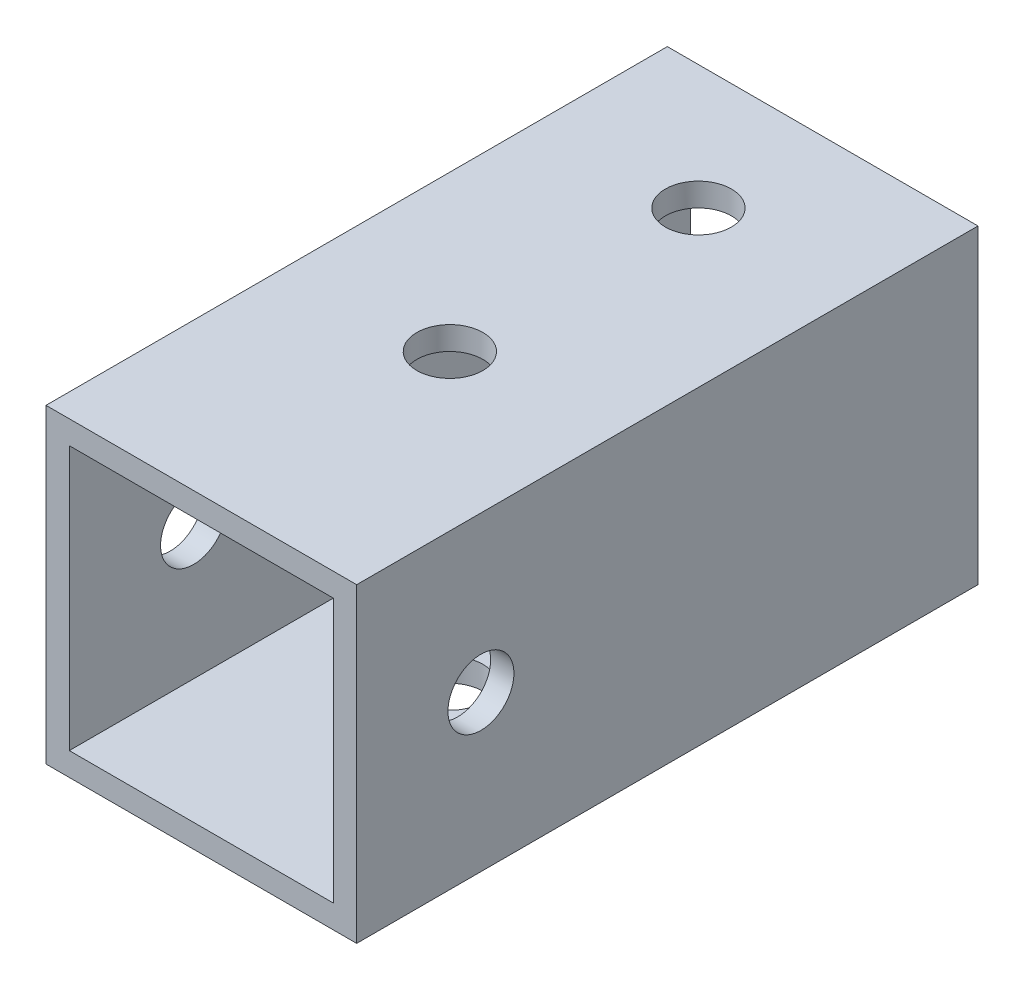
SolidWorks part; units mm, degrees
ref_plane "Front Plane" through (0, 0, 0) normal (0, 0, 1) x (1, 0, 0)
ref_plane "Top Plane" through (0, 0, 0) normal (0, 1, 0) x (1, 0, 0)
ref_plane "Right Plane" through (0, 0, 0) normal (1, 0, 0) x (0, 0, -1)
sketch "Sketch1" plane through (0, 0, 0) normal (0, 0, 1) x (1, 0, 0)
  line L0 (-8.5, -8.5) -> (8.5, -8.5)
  line L1 (-10, -10) -> (10, -10)
  line L2 (-10, -10) -> (-10, 10)
  line L3 (-10, 10) -> (10, 10)
  line L4 (10, -10) -> (10, 10)
  line L5 (-10, -10) -> (10, 10) construction
  line L6 (-10, 10) -> (10, -10) construction
  line L7 (8.5, -8.5) -> (8.5, 8.5)
  line L8 (-8.5, 8.5) -> (8.5, 8.5)
  line L9 (-8.5, -8.5) -> (-8.5, 8.5)
  point P0 (0, 0)
  dimension "D1" = 20
  dimension "D3" = 20
  dimension "D2" = 1.5
extrude "Boss-Extrude1" add sketch "Sketch1" against normal blind 40
sketch "Sketch2" plane through (0, 10, 0) normal (0, 1, 0) x (1, 0, 0)
  line L1 (0, 0) -> (0, 40) construction
  line L4 (10, 40) -> (-10, 40) construction
  circle A1 centre (0, 32) radius 2.125
  circle A2 centre (0, 16) radius 2.125
  dimension "D1" = 8
  dimension "D2" = 4.25
  dimension "D3" = 4.25
  dimension "D4" = 16
extrude "Cut-Extrude1" cut sketch "Sketch2" against normal through all
sketch "Sketch3" plane through (10, 0, 0) normal (1, 0, 0) x (0, 0, -1)
  line L0 (0, 0) -> (40, 0) construction
  line L3 (40, -10) -> (40, 10) construction
  line L4 (0, -10) -> (0, 10) construction
  circle A0 centre (8, 0) radius 2.125
  point P4 (12.0342, 0)
  point P5 (11.7086, 0)
  dimension "D1" = 4.25
  dimension "D2" = 8
extrude "Cut-Extrude2" cut sketch "Sketch3" against normal through all
